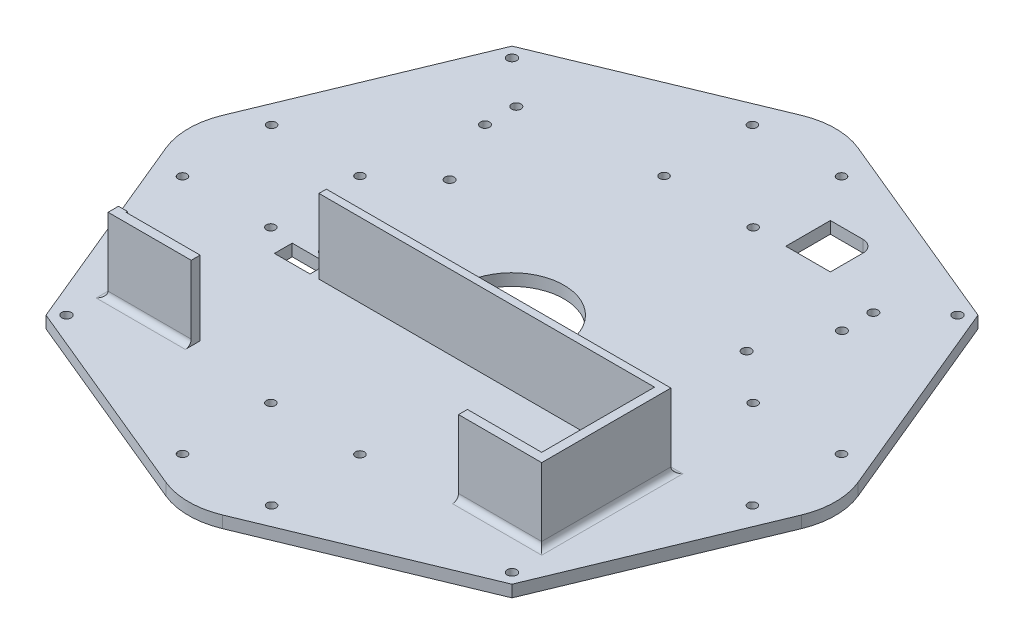
SolidWorks part; units mm, degrees
ref_plane "Front Plane" through (0, 0, 0) normal (0, 0, 1) x (1, 0, 0)
ref_plane "Top Plane" through (0, 0, 0) normal (0, 1, 0) x (1, 0, 0)
ref_plane "Right Plane" through (0, 0, 0) normal (1, 0, 0) x (0, 0, -1)
sketch "Sketch1" plane through (0, 0, 0) normal (0, 1, 0) x (1, 0, 0)
  line L0 (0, -110.9452) -> (78.4501, -78.4501)
  line L7 (0, 110.9452) -> (-78.4501, 78.4501)
  line L8 (-78.4501, 78.4501) -> (-110.9452, 0)
  line L9 (-110.9452, 0) -> (-78.4501, -78.4501)
  line L10 (-78.4501, -78.4501) -> (0, -110.9452)
  line L11 (78.4501, -78.4501) -> (110.9452, 0)
  line L12 (110.9452, 0) -> (78.4501, 78.4501)
  line L13 (78.4501, 78.4501) -> (0, 110.9452)
  circle A0 centre (0, 0) radius 102.5 construction
  dimension "D1" = 205
extrude "Boss-Extrude2" add sketch "Sketch1" along normal blind 4
sketch "Sketch3" plane through (0, 4, 0) normal (0, 1, 0) x (1, 0, 0)
  line L0 (-110.9452, 0) -> (110.9452, 0) construction
  line L1 (0, 110.9452) -> (0, -110.9452) construction
  line L2 (-75, -75) -> (0, 0) construction
  circle A0 centre (-75, -75) radius 1.6
  circle A1 centre (75, -75) radius 1.6
  circle A2 centre (75, 75) radius 1.6
  circle A3 centre (-75, 75) radius 1.6
  point P28 (0, 0)
  dimension "D1" = 3.2
  dimension "D2" = 150
extrude "Cut-Extrude3" cut sketch "Sketch3" against normal through all both and the other way through all
sketch "Sketch6" plane through (0, 4, 0) normal (0, 1, 0) x (1, 0, 0)
  circle A0 centre (0, 0) radius 17.5
  dimension "D1" = 35
extrude "Cut-Extrude6" cut sketch "Sketch6" against normal through all both and the other way through all
sketch "Sketch8" plane through (0, 4, 0) normal (0, 1, 0) x (1, 0, 0)
  line L0 (-15, -66.1952) -> (15, -66.1952) construction
  line L1 (15, -66.1952) -> (15, -95.9452) construction
  line L2 (15, -95.9452) -> (-15, -95.9452) construction
  line L3 (-15, -95.9452) -> (-15, -66.1952) construction
  line L4 (0, 0) -> (0, -66.1952) construction
  line L5 (0, -95.9452) -> (0, -110.9452) construction
  circle A0 centre (-15, -66.1952) radius 1.5
  circle A1 centre (15, -66.1952) radius 1.5
  circle A2 centre (-15, -95.9452) radius 1.5
  circle A3 centre (15, -95.9452) radius 1.5
  dimension "D1" = 3
  dimension "D2" = 29.75
  dimension "D3" = 30
  dimension "D4" = 15
extrude "Cut-Extrude7" cut sketch "Sketch8" against normal up to surface (4 mm away) up to face at (0, 0, 17.5)
pattern_circular "CirPattern1" count 4 over 360 about axis through (0, 4, 0) along (0, 1, 0) of "Cut-Extrude7"
sketch "Sketch10" plane through (0, 4, 0) normal (0, 1, 0) x (1, 0, 0)
  line L0 (-50, 29) -> (50, 29) construction
  line L1 (50, 29) -> (50, -13) construction
  line L2 (50, -13) -> (-50, -13) construction
  line L3 (-50, -13) -> (-50, 29) construction
  line L4 (0, -13) -> (0, 0) construction
  line L5 (-60.1, 51) -> (60.1, 51) construction
  line L6 (-60.1, 51) -> (-60.1, 61.564) construction
  circle A0 centre (-50, 29) radius 1.55
  circle A1 centre (-50, -13) radius 1.55
  circle A2 centre (50, -13) radius 1.55
  circle A3 centre (50, 29) radius 1.55
  circle A7 centre (60.1, 51) radius 1.55
  circle A8 centre (-60.1, 61.564) radius 1.55
  circle A9 centre (60.1, 61.564) radius 1.55
  circle A10 centre (-60.1, 51) radius 1.55
  point P15 (0, 51)
  point P16 (0, 29)
  dimension "D3" = 3.1
  dimension "D7" = 3.1
  dimension "D1" = 100
  dimension "D2" = 42
  dimension "D4" = 22
  dimension "D5" = 13
  dimension "D6" = 120.2
  dimension "D8" = 10.564
extrude "Cut-Extrude8" cut sketch "Sketch10" against normal up to surface (4 mm away) up to face at (-66.1952, 0, 16.5)
sketch "Sketch11" plane through (0, 4, 0) normal (0, 1, 0) x (1, 0, 0)
  line L0 (-73, -19.5) -> (73, -19.5)
  line L1 (-70, -22) -> (70, -22)
  line L2 (-70, -22) -> (-70, -60)
  line L3 (-70, -60) -> (70, -60)
  line L4 (70, -22) -> (70, -60)
  line L5 (73, -19.5) -> (73, -63)
  line L6 (73, -63) -> (-73, -63)
  line L7 (-73, -63) -> (-73, -19.5)
  point P4 (0, -60)
  dimension "D7" = 3
  dimension "D1" = 38
  dimension "D2" = 22
  dimension "D3" = 140
  dimension "D4" = 2.5
  dimension "D5" = 3
  dimension "D6" = 3
extrude "Boss-Extrude4" add sketch "Sketch11" along normal blind 25 contours L7 L0 L5 L6 | L2 L1 L4 L3
sketch "Sketch12" plane through (0, 29, 0) normal (0, 1, 0) x (1, 0, 0)
  line L10 (-73, -19.5) -> (-43, -19.5)
  line L11 (-73, -19.5) -> (73, -19.5) construction
  line L12 (-43, -19.5) -> (-43, -22)
  line L13 (-70, -22) -> (70, -22) construction
  line L14 (-43, -22) -> (-70, -22)
  line L15 (-70, -22) -> (-70, -59.5)
  line L16 (-70, -22) -> (-70, -60) construction
  line L17 (-70, -59.5) -> (-73, -59.5)
  line L18 (-73, -63) -> (-73, -19.5) construction
  line L19 (-73, -59.5) -> (-73, -19.5)
  line L20 (-70, -60) -> (70, -60) construction
  line L21 (-45, -60) -> (45, -60)
  line L22 (-45, -60) -> (-45, -63)
  line L23 (-45, -63) -> (45, -63)
  line L24 (45, -60) -> (45, -63)
  line L25 (73, -63) -> (-73, -63) construction
  line L26 (0, -60) -> (0, 0) construction
  dimension "D1" = 30
  dimension "D2" = 40
  dimension "D3" = 90
extrude "Cut-Extrude9" cut sketch "Sketch12" against normal up to surface (25 mm away) up to face at (0, 4, 41)
fillet "Fillet1" radius 2 5 edges at (59, 4, 63) (73, 4, 41.25) (-73, 4, 61.25) (-59, 4, 63) (15, 4, 19.5)
sketch "Sketch19" plane through (0, 4, 0) normal (0, 1, 0) x (1, 0, 0)
  line L1 (-58.0005, -16) -> (-46.0005, -16)
  line L2 (-58.0005, -16) -> (-58.0005, -22)
  line L3 (-58.0005, -22) -> (-46.0005, -22)
  line L4 (-46.0005, -16) -> (-46.0005, -22)
  line L5 (-43, -22) -> (70, -22) construction
  dimension "D1" = 12
  dimension "D2" = 6
extrude "Cut-Extrude11" cut sketch "Sketch19" against normal through all
sketch "Sketch20" plane through (0, 4, 0) normal (0, 1, 0) x (1, 0, 0)
  line L0 (15, 66.1952) -> (26, 66.1952) construction
  line L1 (41, 66.1952) -> (26, 66.1952)
  line L2 (41, 66.1952) -> (41, 81.1952)
  line L3 (41, 81.1952) -> (26, 81.1952)
  line L4 (26, 66.1952) -> (26, 81.1952)
  dimension "D1" = 15
  dimension "D2" = 15
  dimension "D3" = 11
extrude "Cut-Extrude12" cut sketch "Sketch20" against normal through all both and the other way through all
fillet "Fillet2" radius 25 4 edges at (-110.9452, 2, 0) (0, 2, -110.9452) (110.9452, 2, 0) (0, 2, 110.9452)
fillet "Fillet3" radius 4 1 edges at (41, 2, -81.1952)
